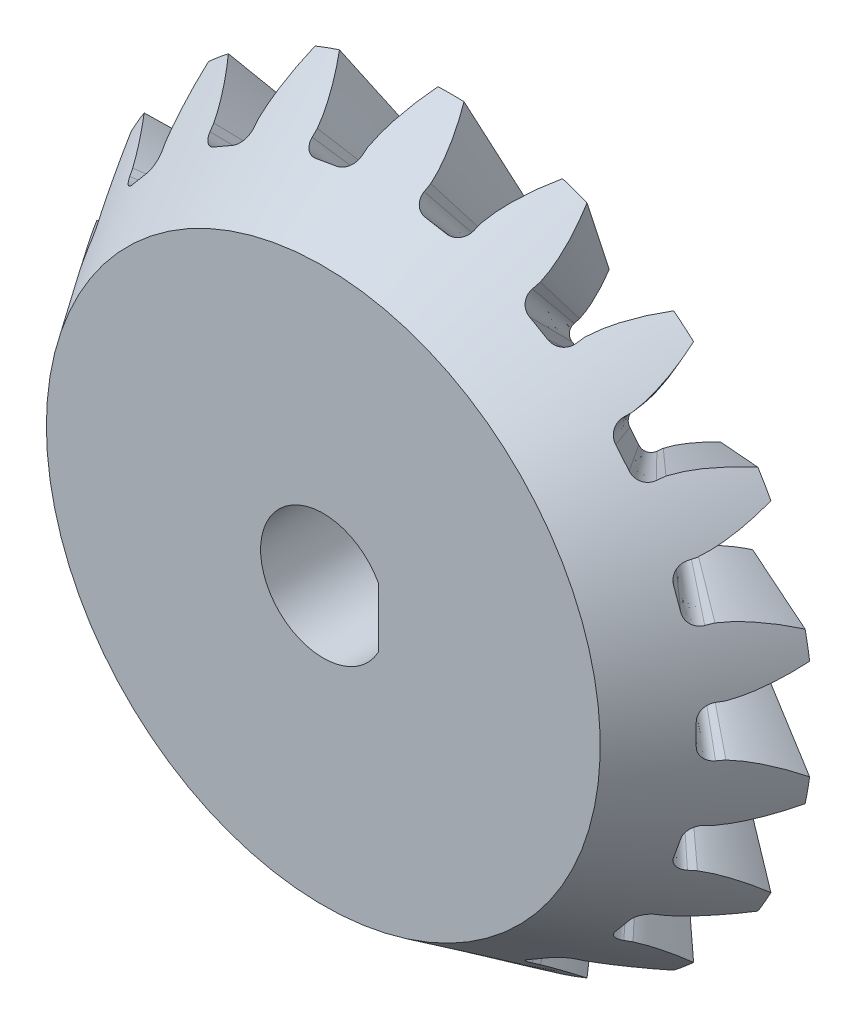
SolidWorks part; units mm, degrees
ref_plane "Front Plane" through (0, 0, 0) normal (0, 0, 1) x (1, 0, 0)
ref_plane "Top Plane" through (0, 0, 0) normal (0, 1, 0) x (1, 0, 0)
ref_plane "Right Plane" through (0, 0, 0) normal (1, 0, 0) x (0, 0, -1)
ref_axis "Gear Axis" through (0, 0, -1.3521) along (0, 0, 1)
sketch "Blank Sketch" plane through (0, 0, 0) normal (0, 1, 0) x (1, 0, 0)
  line L0 (0, 0) -> (0, -27.0416) construction
  line L1 (0, 0) -> (22.5, -15) construction
  line L2 (0, 0) -> (15.0115, -10.0077) construction
  line L3 (11.176, -15.7611) -> (15.6135, -9.1047)
  line L4 (15.6135, -9.1047) -> (23.5324, -13.4515)
  line L5 (23.5324, -13.4515) -> (17.9981, -21.7528)
  line L6 (17.9981, -21.7528) -> (4.075, -21.7528)
  line L7 (4.075, -21.7528) -> (4.075, -15.7611)
  line L8 (4.075, -15.7611) -> (11.176, -15.7611)
  line L9 (22.5, -15) -> (23.5324, -13.4515) construction
  line L10 (22.5, -15) -> (17.9981, -21.7528) construction
  line L11 (15.0115, -10.0077) -> (11.176, -15.7611) construction
  dimension "Axis" = 27.0416
  dimension "Cone" = 56.31
  dimension "Heel" = 27.0416
  dimension "Toe Cone" = 56.31
  dimension "Toe" = 18.0416
  dimension "Heel Square" = 90
  dimension "Addendum" = 1.8611
  dimension "Root Square" = 90
  dimension "Heel Rim" = 8.1158
  dimension "Toe Square" = 90
  dimension "Toe Rim" = 6.9147
  dimension "Front Square" = 90
  dimension "Face" = 4.927
  dimension "Back" = 13.9231
  dimension "Front" = 7.101
revolve "Blank" add sketch "Blank Sketch" angle 360 about L0
sketch "Cone Sketch" plane through (0, 0, 0) normal (0, 1, 0) x (1, 0, 0)
  line L0 (0, 0) -> (0, -27.0416) construction
  line L1 (0, 0) -> (24.5801, -16.3868)
  line L2 (0, 0) -> (12.9314, -8.6209)
  dimension "Axis" = 27.0416
  dimension "Toe Cone" = 56.31
  dimension "Heel Cone" = 56.31
  dimension "Heel" = 29.5416
  dimension "Toe" = 15.5416
ref_plane "Heel Plane" through (24.5801, 0, 16.3868) normal (0.8321, 0, 0.5547) x (0.5547, 0, -0.8321)
ref_plane "Toe Plane" through (12.9314, 0, 8.6209) normal (0.8321, 0, 0.5547) x (0.5547, 0, -0.8321)
sketch "Heel Section Sketch" plane through (24.5801, 0, 16.3868) normal (0.8321, 0, 0.5547) x (0.5547, 0, -0.8321)
  line L0 (0, 0) -> (-44.3125, 0) construction
  line L1 (-2.4254, 1.822) -> (-2.9568, 1.7989)
  line L2 (-2.4254, -1.822) -> (-2.9568, -1.7989)
  line L3 (4.4731, 5.3382) -> (4.4731, -5.3382)
  arc A0 (-2.9568, 1.7989) -> (-3.9494, 0.7429) centre (-2.9117, 0.762) ccw
  arc A1 (-3.9494, -0.7429) -> (-2.9568, -1.7989) centre (-2.9117, -0.762) ccw
  arc A2 (-3.9494, -0.7429) -> (-3.9494, 0.7429) centre (-44.3125, 0) ccw
  spline S0 degree 4 poles (-2.6185, 1.7952) (-2.5735, 1.8001) (-2.4634, 1.8153) (-2.3826, 1.8283) (-2.1666, 1.8686) (-2.0036, 1.9057) (-1.7812, 1.9593) (-1.5664, 2.0195) (-1.329, 2.0902) (-1.1027, 2.1645) (-0.8722, 2.2444) (-0.6468, 2.3281) (-0.412, 2.4198) (-0.1247, 2.538) (0.217, 2.6881) (0.607, 2.871) (1.0408, 3.0905) (1.4634, 3.3174) (1.8882, 3.5612) (2.2942, 3.8046) (2.7157, 4.0742) (3.0965, 4.325) (3.5292, 4.6295) (3.8609, 4.867) (4.3217, 5.2186) (4.5362, 5.3868) (4.8006, 5.5995) (4.951, 5.7231) (5.0219, 5.782) (5.0608, 5.8144) (5.0806, 5.831) knots 0 0 0 0 0 0.022117 0.039787 0.058126 0.081614 0.109122 0.13663 0.164138 0.191645 0.219153 0.246661 0.274169 0.305931 0.360947 0.415962 0.470978 0.525993 0.581009 0.636024 0.69104 0.746055 0.801071 0.856086 0.911102 0.955551 0.977775 0.988888 1 1 1 1 1 construction
  spline S1 degree 4 poles (-2.4254, 1.822) (-2.3913, 1.8275) (-2.324, 1.8392) (-2.1666, 1.8686) (-2.0036, 1.9057) (-1.7812, 1.9593) (-1.5664, 2.0195) (-1.329, 2.0902) (-1.1027, 2.1645) (-0.8722, 2.2444) (-0.6468, 2.3281) (-0.412, 2.4198) (-0.1247, 2.538) (0.217, 2.6881) (0.607, 2.871) (1.0408, 3.0905) (1.4634, 3.3174) (1.8882, 3.5612) (2.2942, 3.8046) (2.7157, 4.0742) (3.0965, 4.325) (3.5292, 4.6295) (3.8609, 4.867) (4.2239, 5.144) (4.3887, 5.2717) (4.4731, 5.3382) knots 0.022117 0.022117 0.022117 0.022117 0.022117 0.039787 0.058126 0.081614 0.109122 0.13663 0.164138 0.191645 0.219153 0.246661 0.274169 0.305931 0.360947 0.415962 0.470978 0.525993 0.581009 0.636024 0.69104 0.746055 0.801071 0.856086 0.911102 0.911102 0.911102 0.911102 0.911102
  spline S2 degree 4 poles (-2.6185, -1.7952) (-2.5735, -1.8001) (-2.4634, -1.8153) (-2.3826, -1.8283) (-2.1666, -1.8686) (-2.0036, -1.9057) (-1.7812, -1.9593) (-1.5664, -2.0195) (-1.329, -2.0902) (-1.1027, -2.1645) (-0.8722, -2.2444) (-0.6468, -2.3281) (-0.412, -2.4198) (-0.1247, -2.538) (0.217, -2.6881) (0.607, -2.871) (1.0408, -3.0905) (1.4634, -3.3174) (1.8882, -3.5612) (2.2942, -3.8046) (2.7157, -4.0742) (3.0965, -4.325) (3.5292, -4.6295) (3.8609, -4.867) (4.3217, -5.2186) (4.5362, -5.3868) (4.8006, -5.5995) (4.951, -5.7231) (5.0219, -5.782) (5.0608, -5.8144) (5.0806, -5.831) knots 0 0 0 0 0 0.022117 0.039787 0.058126 0.081614 0.109122 0.13663 0.164138 0.191645 0.219153 0.246661 0.274169 0.305931 0.360947 0.415962 0.470978 0.525993 0.581009 0.636024 0.69104 0.746055 0.801071 0.856086 0.911102 0.955551 0.977775 0.988888 1 1 1 1 1 construction
  spline S3 degree 4 poles (-2.4254, -1.822) (-2.3913, -1.8275) (-2.324, -1.8392) (-2.1666, -1.8686) (-2.0036, -1.9057) (-1.7812, -1.9593) (-1.5664, -2.0195) (-1.329, -2.0902) (-1.1027, -2.1645) (-0.8722, -2.2444) (-0.6468, -2.3281) (-0.412, -2.4198) (-0.1247, -2.538) (0.217, -2.6881) (0.607, -2.871) (1.0408, -3.0905) (1.4634, -3.3174) (1.8882, -3.5612) (2.2942, -3.8046) (2.7157, -4.0742) (3.0965, -4.325) (3.5292, -4.6295) (3.8609, -4.867) (4.2239, -5.144) (4.3887, -5.2717) (4.4731, -5.3382) knots 0.022117 0.022117 0.022117 0.022117 0.022117 0.039787 0.058126 0.081614 0.109122 0.13663 0.164138 0.191645 0.219153 0.246661 0.274169 0.305931 0.360947 0.415962 0.470978 0.525993 0.581009 0.636024 0.69104 0.746055 0.801071 0.856086 0.911102 0.911102 0.911102 0.911102 0.911102
  dimension "Root" = 40.3699
  dimension "Fillet" = 1.0378
  dimension "Centre" = 44.3125
sketch "Toe Section Sketch" plane through (12.9314, 0, 8.6209) normal (0.8321, 0, 0.5547) x (0.5547, 0, -0.8321)
  line L0 (0, 0) -> (-23.3125, 0) construction
  line L1 (-1.276, 0.9585) -> (-1.5556, 0.9464)
  line L2 (-1.276, -0.9585) -> (-1.5556, -0.9464)
  line L3 (2.3533, 2.8084) -> (2.3533, -2.8084)
  arc A0 (-1.5556, 0.9464) -> (-2.0777, 0.3908) centre (-1.5318, 0.4009) ccw
  arc A1 (-2.0777, -0.3908) -> (-1.5556, -0.9464) centre (-1.5318, -0.4009) ccw
  arc A2 (-2.0777, -0.3908) -> (-2.0777, 0.3908) centre (-23.3125, 0) ccw
  spline S0 degree 4 poles (-1.3801, 0.944) (-1.3498, 0.9477) (-1.2981, 0.9547) (-1.2515, 0.9622) (-1.1417, 0.9827) (-1.0525, 1.0029) (-0.9382, 1.0306) (-0.8233, 1.0626) (-0.6997, 1.0996) (-0.5798, 1.1388) (-0.459, 1.1807) (-0.3402, 1.2248) (-0.2168, 1.273) (-0.0656, 1.3353) (0.1141, 1.4142) (0.3193, 1.5104) (0.5475, 1.6259) (0.7699, 1.7453) (0.9934, 1.8735) (1.207, 2.0016) (1.4287, 2.1434) (1.6291, 2.2754) (1.8566, 2.4355) (2.0313, 2.5606) (2.2734, 2.7453) (2.4008, 2.8452) (2.5617, 2.975) (2.632, 3.0335) (2.6721, 3.067) knots 0 0 0 0 0 0.022117 0.039787 0.058126 0.081614 0.109122 0.13663 0.164138 0.191645 0.219153 0.246661 0.274169 0.305931 0.360947 0.415962 0.470978 0.525993 0.581009 0.636024 0.69104 0.746055 0.801071 0.856086 0.911102 0.955551 1 1 1 1 1 construction
  spline S1 degree 4 poles (-1.276, 0.9585) (-1.2581, 0.9614) (-1.2218, 0.9678) (-1.1417, 0.9827) (-1.0525, 1.0029) (-0.9382, 1.0306) (-0.8233, 1.0626) (-0.6997, 1.0996) (-0.5798, 1.1388) (-0.459, 1.1807) (-0.3402, 1.2248) (-0.2168, 1.273) (-0.0656, 1.3353) (0.1141, 1.4142) (0.3193, 1.5104) (0.5475, 1.6259) (0.7699, 1.7453) (0.9934, 1.8735) (1.207, 2.0016) (1.4287, 2.1434) (1.6291, 2.2754) (1.8566, 2.4355) (2.0313, 2.5606) (2.2221, 2.7061) (2.3088, 2.7734) (2.3533, 2.8084) knots 0.022117 0.022117 0.022117 0.022117 0.022117 0.039787 0.058126 0.081614 0.109122 0.13663 0.164138 0.191645 0.219153 0.246661 0.274169 0.305931 0.360947 0.415962 0.470978 0.525993 0.581009 0.636024 0.69104 0.746055 0.801071 0.856086 0.911102 0.911102 0.911102 0.911102 0.911102
  spline S2 degree 4 poles (-1.3801, -0.944) (-1.3498, -0.9477) (-1.2981, -0.9547) (-1.2515, -0.9622) (-1.1417, -0.9827) (-1.0525, -1.0029) (-0.9382, -1.0306) (-0.8233, -1.0626) (-0.6997, -1.0996) (-0.5798, -1.1388) (-0.459, -1.1807) (-0.3402, -1.2248) (-0.2168, -1.273) (-0.0656, -1.3353) (0.1141, -1.4142) (0.3193, -1.5104) (0.5475, -1.6259) (0.7699, -1.7453) (0.9934, -1.8735) (1.207, -2.0016) (1.4287, -2.1434) (1.6291, -2.2754) (1.8566, -2.4355) (2.0313, -2.5606) (2.2734, -2.7453) (2.4008, -2.8452) (2.5617, -2.975) (2.632, -3.0335) (2.6721, -3.067) knots 0 0 0 0 0 0.022117 0.039787 0.058126 0.081614 0.109122 0.13663 0.164138 0.191645 0.219153 0.246661 0.274169 0.305931 0.360947 0.415962 0.470978 0.525993 0.581009 0.636024 0.69104 0.746055 0.801071 0.856086 0.911102 0.955551 1 1 1 1 1 construction
  spline S3 degree 4 poles (-1.276, -0.9585) (-1.2581, -0.9614) (-1.2218, -0.9678) (-1.1417, -0.9827) (-1.0525, -1.0029) (-0.9382, -1.0306) (-0.8233, -1.0626) (-0.6997, -1.0996) (-0.5798, -1.1388) (-0.459, -1.1807) (-0.3402, -1.2248) (-0.2168, -1.273) (-0.0656, -1.3353) (0.1141, -1.4142) (0.3193, -1.5104) (0.5475, -1.6259) (0.7699, -1.7453) (0.9934, -1.8735) (1.207, -2.0016) (1.4287, -2.1434) (1.6291, -2.2754) (1.8566, -2.4355) (2.0313, -2.5606) (2.2221, -2.7061) (2.3088, -2.7734) (2.3533, -2.8084) knots 0.022117 0.022117 0.022117 0.022117 0.022117 0.039787 0.058126 0.081614 0.109122 0.13663 0.164138 0.191645 0.219153 0.246661 0.274169 0.305931 0.360947 0.415962 0.470978 0.525993 0.581009 0.636024 0.69104 0.746055 0.801071 0.856086 0.911102 0.911102 0.911102 0.911102 0.911102
  dimension "Root" = 21.2383
  dimension "Fillet" = 0.546
  dimension "Centre" = 23.3125
loft "Tooth Space" cut profiles "Heel Section Sketch", "Toe Section Sketch"
pattern_circular "Teeth" count 18 over 360 about axis through (0, 0, -1.3521) along (0, 0, 1) of "Tooth Space"
sketch "D-Flat Sketch" plane through (0, 0, 0) normal (0, 0, 1) x (1, 0, 0)
  line L0 (3.575, -2.3894) -> (3.575, 2.3894)
  arc A0 (3.575, -2.3894) -> (3.575, 2.3894) centre (0, 0) ccw
sketch "Sketch2" plane through (0, 0, 0) normal (0, 0, 1) x (1, 0, 0)
  line L0 (3.575, -2.3894) -> (3.575, 2.3894)
  arc A0 (3.575, -2.3894) -> (3.575, 2.3894) centre (0, 0) ccw
extrude "D-Flat" add sketch "Sketch2" along normal blind 5.9917 from offset 15.7611
equation "\"No. of Teeth\"= 18"
equation "\"Module\"= 2.5"
equation "\"Bore Diameter\"= 8.15"
equation "\"Pressure Angle\"= 20"
equation "\"Shaft Angle\"= 90"
equation "\"Mate Teeth\"= 12"
equation "\"Pitch Cone Angle\"= IIF ( ( \"Mate Teeth\" / \"No. of Teeth\" + cos ( \"Shaft Angle\" ) ) > 0 , atn ( sin ( \"Shaft Angle\" ) / ( \"Mate Teeth\" / \"No. of Teeth\" + cos ( \"Shaft Angle\" ) ) ) , 180 + atn ( sin ( \"Shaft Angle\" ) / ( \"Mate Teeth\" / \"No. of Teeth\" + cos ( \"Shaft Angle\" ) ) ) )"
equation "\"Mate Cone Angle\"= \"Shaft Angle\" - \"Pitch Cone Angle\""
equation "\"Addendum\"= IIF ( \"No. of Teeth\" >= \"Mate Teeth\" , 0.54 * \"Module\" + 0.46 * \"Module\" / ( ( \"No. of Teeth\" * cos ( \"Mate Cone Angle\" ) ) / ( \"Mate Teeth\" * cos ( \"Pitch Cone Angle\" ) ) ) , 2 * \"Module\" - ( 0.54 * \"Module\" + 0.46 * \"Module\" / ( ( \"Mate Teeth\" * cos ( \"Pitch Cone Angle\" ) ) / ( \"No. of Teeth\" * cos ( \"Mate Cone Angle\" ) ) ) ) )"
equation "\"Outer Diameter\"= \"No. of Teeth\" * \"Module\" + 2 * \"Addendum\" * cos ( \"Pitch Cone Angle\" )"
equation "\"Pitch Diameter\"= \"No. of Teeth\" * \"Module\""
equation "\"Backlash\"= IIF ( \"Module\" <= 1 , 0.3 * \"Module\" , 0.3 )"
equation "\"Arc Length\"= ( ( \"Module\" * pi ) / 2 + \"Backlash\" - 2 * ( \"Addendum\" - \"Module\" ) * tan ( \"Pressure Angle\" ) )"
equation "\"Fillet Radius\"= 0.38 * \"Module\""
equation "\"Mate Addendum\"= 2 * \"Module\" - \"Addendum\""
equation "\"Dedendum\"= 2.188 * \"Module\" - \"Addendum\""
equation "\"Tooth Depth\"= \"Addendum\" + \"Dedendum\""
equation "\"Mate Dedendum\"= 2.188 * \"Module\" - \"Mate Addendum\""
equation "\"Face Width\"= 9"
equation "\"Cone Distance\"= \"Pitch Diameter\" / ( 2 * sin ( \"Pitch Cone Angle\" ) )"
equation "\"Dedendum Angle\"= atn ( \"Dedendum\" / \"Cone Distance\" )"
equation "\"Mate Dedendum Angle\"= atn ( \"Mate Dedendum\" / \"Cone Distance\" )"
equation "\"Face Angle\"= \"Pitch Cone Angle\" + \"Mate Dedendum Angle\""
equation "\"Root Angle\"= \"Pitch Cone Angle\" - \"Dedendum Angle\""
equation "\"Overrun\"= \"Module\""
equation "\"Back Cone Pitch Diameter\"= \"Pitch Diameter\" / cos ( \"Pitch Cone Angle\" )"
equation "\"Back Cone Outer Diameter\"= \"Back Cone Pitch Diameter\" + 2 * \"Addendum\""
equation "\"Root Diameter\"= \"Back Cone Outer Diameter\" - 2 * \"Tooth Depth\""
equation "\"Base Diameter\"= \"Back Cone Pitch Diameter\" * cos ( \"Pressure Angle\" )"
equation "\"Base Radius\"= \"Base Diameter\" / 2"
equation "\"Tooth Thickness\"= \"Module\" * pi - \"Arc Length\""
equation "\"Half Space Angle\"= ( \"Arc Length\" / \"Back Cone Pitch Diameter\" ) * 180 / pi"
equation "\"Involute Fn\"= tan ( \"Pressure Angle\" ) - \"Pressure Angle\" * pi / 180"
equation "\"Flank Offset\"= \"Arc Length\" / \"Back Cone Pitch Diameter\" - \"Involute Fn\""
equation "\"Tip Cap Diameter\"= \"Back Cone Outer Diameter\" + 2 * \"Module\""
equation "\"Flank Start Diameter\"= IIF ( \"Base Diameter\" >= ( \"Root Diameter\" + 3 * \"Fillet Radius\" ) , \"Base Diameter\" , \"Root Diameter\" + 3 * \"Fillet Radius\" )"
equation "\"Involute t1\"= ( abs ( ( \"Flank Start Diameter\" / \"Base Diameter\" ) ^ 2 - 1 ) ) ^ 0.5"
equation "\"Involute t2\"= ( abs ( ( \"Tip Cap Diameter\" / \"Base Diameter\" ) ^ 2 - 1 ) ) ^ 0.5"
equation "\"Flank Arc Radius\"= ( \"Back Cone Pitch Diameter\" / 2 ) * sin ( \"Pressure Angle\" )"
equation "\"Flank Centre Angle\"= \"Half Space Angle\" + \"Pressure Angle\""
equation "\"Heel Distance\"= \"Cone Distance\" + \"Overrun\""
equation "\"Toe Distance\"= \"Cone Distance\" - \"Face Width\" - \"Overrun\""
equation "\"Heel Scale\"= \"Heel Distance\" / \"Cone Distance\""
equation "\"Toe Scale\"= \"Toe Distance\" / \"Cone Distance\""
equation "\"Heel Virtual Radius\"= \"Heel Distance\" * tan ( \"Pitch Cone Angle\" )"
equation "\"Toe Virtual Radius\"= \"Toe Distance\" * tan ( \"Pitch Cone Angle\" )"
equation "\"Axis@Blank Sketch\"= \"Cone Distance\""
equation "\"Cone@Blank Sketch\"= \"Pitch Cone Angle\""
equation "\"Heel@Blank Sketch\"= \"Cone Distance\""
equation "\"Toe Cone@Blank Sketch\"= \"Pitch Cone Angle\""
equation "\"Toe@Blank Sketch\"= \"Cone Distance\" - \"Face Width\""
equation "\"Addendum@Blank Sketch\"= \"Addendum\""
equation "\"Heel Rim@Blank Sketch\"= \"Dedendum\" + \"Module\" / cos ( \"Pitch Cone Angle\" )"
equation "\"Toe Rim@Blank Sketch\"= \"Dedendum\" - \"Face Width\" * tan ( \"Dedendum Angle\" ) + \"Module\" / cos ( \"Pitch Cone Angle\" )"
equation "\"Face@Blank Sketch\"= \"Mate Dedendum Angle\""
equation "\"Back@Blank Sketch\"= \"Cone Distance\" * sin ( \"Pitch Cone Angle\" ) - \"Dedendum\" * cos ( \"Pitch Cone Angle\" ) - \"Module\" - \"Bore Diameter\" / 2"
equation "\"Front@Blank Sketch\"= ( \"Cone Distance\" - \"Face Width\" ) * sin ( \"Pitch Cone Angle\" ) - ( \"Dedendum\" - \"Face Width\" * tan ( \"Dedendum Angle\" ) + \"Module\" / cos ( \"Pitch Cone Angle\" ) ) * cos ( \"Pitch Cone Angle\" ) - \"Bore Diameter\" / 2"
equation "\"Axis@Cone Sketch\"= \"Cone Distance\""
equation "\"Heel Cone@Cone Sketch\"= \"Pitch Cone Angle\""
equation "\"Heel@Cone Sketch\"= \"Heel Distance\""
equation "\"Toe Cone@Cone Sketch\"= \"Pitch Cone Angle\""
equation "\"Toe@Cone Sketch\"= \"Toe Distance\""
equation "\"Centre@Heel Section Sketch\"= \"Heel Virtual Radius\""
equation "\"Root@Heel Section Sketch\"= ( \"Root Diameter\" / 2 ) * \"Heel Scale\""
equation "\"Fillet@Heel Section Sketch\"= ( \"Fillet Radius\" ) * \"Heel Scale\""
equation "\"Centre@Toe Section Sketch\"= \"Toe Virtual Radius\""
equation "\"Root@Toe Section Sketch\"= ( \"Root Diameter\" / 2 ) * \"Toe Scale\""
equation "\"Fillet@Toe Section Sketch\"= ( \"Fillet Radius\" ) * \"Toe Scale\""
equation "\"Count@Teeth\"= \"No. of Teeth\""
